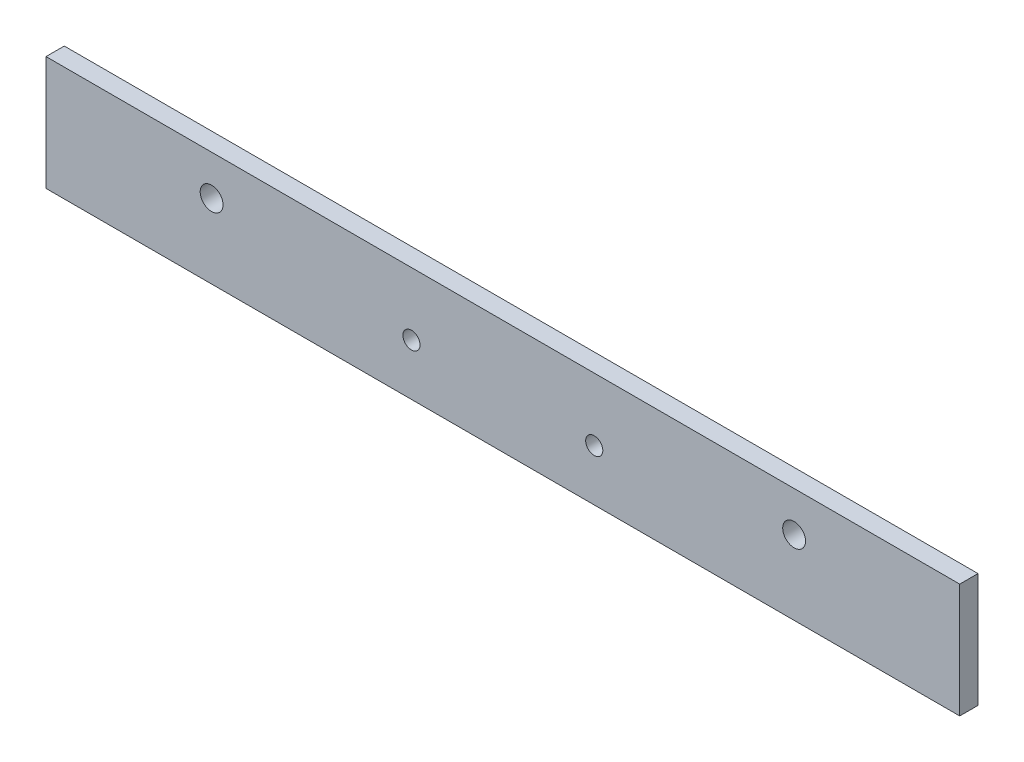
SolidWorks part; units mm, degrees
ref_plane "Front Plane" through (0, 0, 0) normal (0, 0, 1) x (1, 0, 0)
ref_plane "Top Plane" through (0, 0, 0) normal (0, 1, 0) x (1, 0, 0)
ref_plane "Right Plane" through (0, 0, 0) normal (1, 0, 0) x (0, 0, -1)
ref_plane "Plane1" through (0, 0, 10) normal (0, 0, 1) x (1, 0, 0)
sketch "Sketch2" plane through (0, -10, 10) normal (0, 0, -1) x (1, 0, 0)
  line L1 (0, -10) -> (160, -10)
  line L2 (0, -10) -> (0, 10)
  line L3 (0, 10) -> (160, 10)
  line L4 (160, -10) -> (160, 10)
  dimension "D1" = 20
  dimension "D2" = 160
extrude "Boss-Extrude1" add sketch "Sketch2" along normal blind 3.2
sketch "Sketch4" plane through (0, 0, 0) normal (0, 1, 0) x (1, 0, 0)
  line L0 (0, -10) -> (160, -10) construction
  line L1 (0, -6.8) -> (80, -6.8)
  line L2 (0, -6.8) -> (0, -10)
  line L3 (0, -10) -> (80, -10)
  line L4 (80, -6.8) -> (80, -10)
  line L5 (160, -6.8) -> (160, -10) construction
  dimension "D1" = 80
  dimension "D2" = 80
sketch "Sketch5" plane through (0, 0, 10) normal (0, 0, 1) x (1, 0, 0)
  line L0 (102, 2.15) -> (102, -20)
  line L1 (102, 0) -> (102, 4.3) construction
  line L2 (160, -20) -> (0, -20) construction
  line L3 (58, 2.15) -> (58, -20)
  line L4 (58, 0) -> (58, 4.3) construction
  line L7 (29, -7) -> (131, -7)
  line L9 (0, 0) -> (160, 0) construction
  circle A0 centre (131, -7) radius 2
  circle A1 centre (29, -7) radius 2
  dimension "D1" = 7
extrude "Cut-Extrude1" cut sketch "Sketch5" against normal through all both and the other way through all contours A0 | A1
sketch "Sketch6" plane through (0, 0, 10) normal (0, 0, 1) x (1, 0, 0)
  circle A0 centre (64, -11) radius 1.5
  circle A1 centre (96, -11) radius 1.5
  dimension "D1" = 32
extrude "Cut-Extrude2" cut sketch "Sketch6" against normal blind 10
